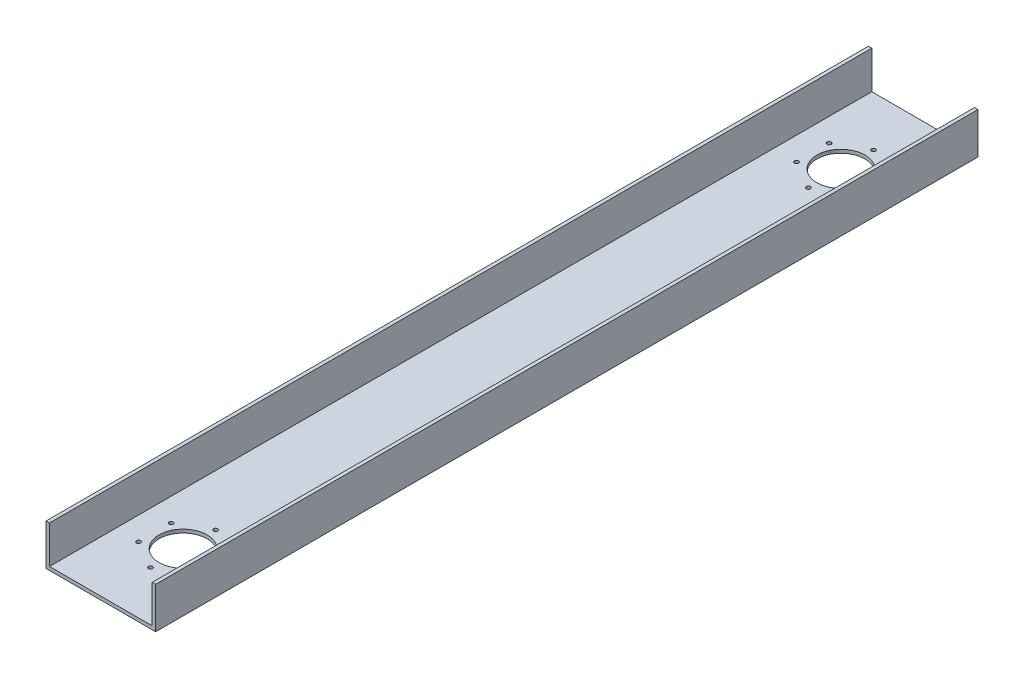
SolidWorks part; units mm, degrees
ref_plane "Front" through (0, 0, 0) normal (0, 0, 1) x (1, 0, 0)
ref_plane "Top" through (0, 0, 0) normal (0, 1, 0) x (1, 0, 0)
ref_plane "Right" through (0, 0, 0) normal (1, 0, 0) x (0, 0, -1)
sketch "Sketch1" plane through (0, 0, 0) normal (0, 0, 1) x (1, 0, 0)
  line L0 (3.175, 3.175) -> (3.175, 38.1)
  line L1 (0, 0) -> (101.6, 0)
  line L2 (0, 0) -> (0, 38.1)
  line L4 (101.6, 0) -> (101.6, 38.1)
  line L5 (3.175, 3.175) -> (98.425, 3.175)
  line L6 (98.425, 3.175) -> (98.425, 38.1)
  line L7 (0, 38.1) -> (3.175, 38.1)
  line L8 (101.6, 38.1) -> (98.425, 38.1)
  dimension "D1" = 38.1
  dimension "D2" = 101.6
  dimension "D3" = 3.175
extrude "Boss-Extrude1" add sketch "Sketch1" along normal blind 762
sketch "Sketch2" plane through (0, 0, 0) normal (0, -1, 0) x (1, 0, 0)
  line L0 (50.8, 762) -> (50.8, 685.8) construction
  line L1 (0, 762) -> (101.6, 762) construction
  circle A0 centre (50.8, 685.8) radius 22.2377
  dimension "D2" = 44.4754
  dimension "D1" = 76.2
extrude "Cut-Extrude1" cut sketch "Sketch2" against normal up to next
sketch "Sketch3" plane through (0, 0, 0) normal (0, -1, 0) x (1, 0, 0)
  line L0 (50.8, 685.8) -> (50.8, 715.9625) construction
  circle A0 centre (50.8, 715.9625) radius 1.8987
  circle A1 centre (76.9215, 700.8813) radius 1.8987
  circle A2 centre (76.9215, 670.7188) radius 1.8986
  circle A3 centre (50.8, 655.6375) radius 1.8987
  circle A4 centre (24.6785, 670.7187) radius 1.8987
  circle A5 centre (24.6785, 700.8812) radius 1.8987
  point P17 (50.8, 685.8)
  dimension "D2" = 3.7973
  dimension "D1" = 30.1625
  dimension "D3" = 6
extrude "Cut-Extrude2" cut sketch "Sketch3" against normal up to next
ref_plane "Mid_Plane" through (0, 0, 381) normal (0, 0, 1) x (1, 0, 0)
mirror "Mirror1" about plane through (0, 0, 381) normal (0, 0, 1) of "Cut-Extrude2", "Cut-Extrude1"
